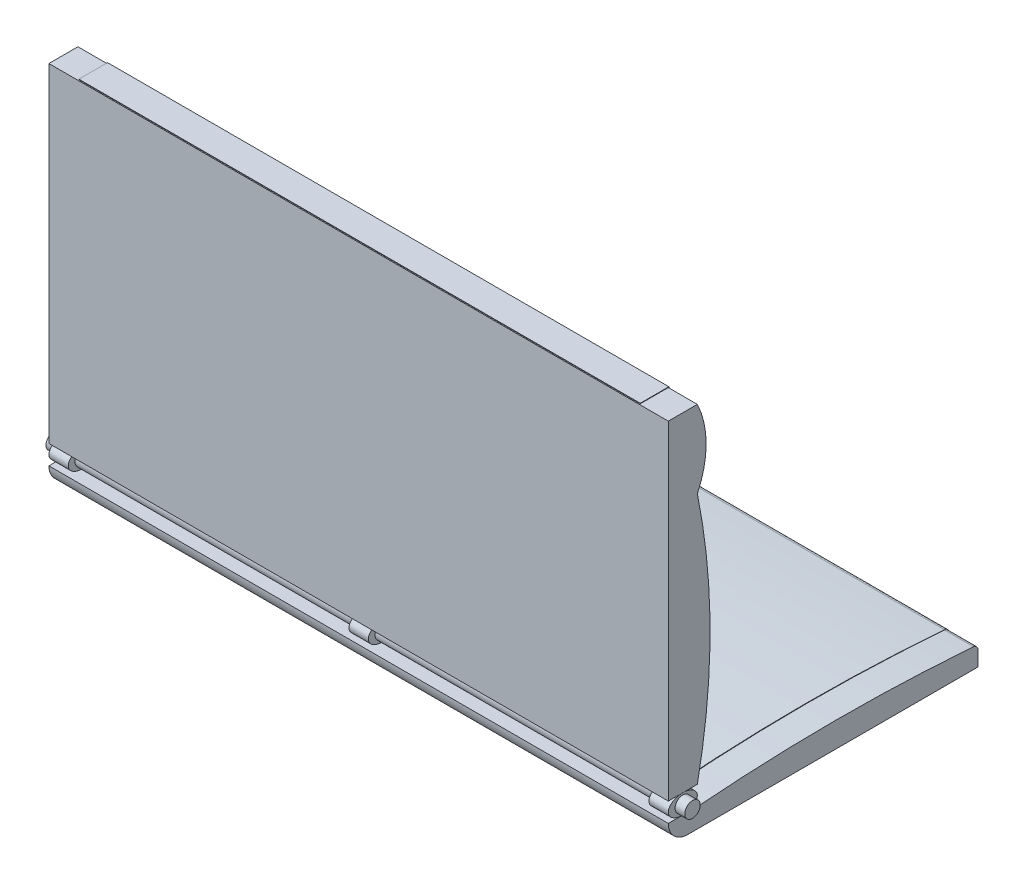
SolidWorks part; units mm, degrees
ref_plane "Front Plane" through (0, 0, 0) normal (0, 0, 1) x (1, 0, 0)
ref_plane "Top Plane" through (0, 0, 0) normal (0, 1, 0) x (1, 0, 0)
ref_plane "Right Plane" through (0, 0, 0) normal (1, 0, 0) x (0, 0, -1)
sketch "Sketch2" plane through (0, 0, 0) normal (0, 1, 0) x (1, 0, 0)
  line L1 (-406.4, -203.2) -> (406.4, -203.2)
  line L2 (-406.4, -203.2) -> (-406.4, 203.2)
  line L3 (-406.4, 203.2) -> (406.4, 203.2)
  line L4 (406.4, -203.2) -> (406.4, 203.2)
  line L5 (-406.4, -203.2) -> (406.4, 203.2) construction
  line L6 (-406.4, 203.2) -> (406.4, -203.2) construction
  point P0 (0, 0)
extrude "Boss-Extrude1" add sketch "Sketch2" along normal blind 25.4
sketch "Sketch3" plane through (0, 25.4, 0) normal (0, 1, 0) x (1, 0, 0)
  line L0 (406.4, -203.2) -> (406.4, 203.2) construction
  line L1 (-406.4, -203.2) -> (406.4, -203.2)
  line L2 (-406.4, -203.2) -> (-406.4, -165.1)
  line L3 (-406.4, -165.1) -> (406.4, -165.1)
  line L4 (406.4, -203.2) -> (406.4, -165.1)
extrude "Boss-Extrude2" add sketch "Sketch3" along normal blind 431.8 from offset 25.4 separate body
sketch "Sketch4" plane through (406.4, 0, 0) normal (1, 0, 0) x (0, 0, -1)
  line L0 (-203.2, 50.8) -> (-203.2, 25.4) construction
  line L1 (-203.2, 25.4) -> (-165.1, 50.8) construction
  line L2 (-165.1, 50.8) -> (-165.1, 25.4) construction
  line L3 (-203.2, 25.4) -> (203.2, 25.4) construction
  line L4 (-165.1, 25.4) -> (-203.2, 50.8) construction
  line L5 (-203.2, 50.8) -> (-165.1, 50.8) construction
  ellipse E0 centre (-184.15, 38.1) end of major axis (-203.2, 38.1) minor radius 12.7
extrude "Boss-Extrude3" add sketch "Sketch4" against normal blind 25.4 separate body
sketch "Sketch6" plane through (-406.4, 0, 0) normal (-1, 0, 0) x (0, 0, 1)
  line L0 (203.2, 50.8) -> (203.2, 25.4) construction
  line L1 (203.2, 25.4) -> (165.1, 50.8) construction
  line L2 (165.1, 50.8) -> (165.1, 25.4) construction
  line L3 (-203.2, 25.4) -> (203.2, 25.4) construction
  line L4 (165.1, 25.4) -> (203.2, 50.8) construction
  line L5 (165.1, 50.8) -> (203.2, 50.8) construction
  ellipse E0 centre (184.15, 38.1) end of major axis (203.2, 38.1) minor radius 12.7
extrude "Boss-Extrude4" add sketch "Sketch6" against normal blind 25.4 separate body
sketch "Sketch7" plane through (406.4, 0, 0) normal (1, 0, 0) x (0, 0, -1)
  line L0 (-203.2, 50.8) -> (-203.2, 25.4) construction
  line L1 (-203.2, 25.4) -> (-165.1, 50.8) construction
  line L2 (-165.1, 50.8) -> (-165.1, 25.4) construction
  line L3 (-203.2, 25.4) -> (203.2, 25.4) construction
  line L4 (-165.1, 25.4) -> (-203.2, 50.8) construction
  line L5 (-203.2, 50.8) -> (-165.1, 50.8) construction
  ellipse E0 centre (-184.15, 38.1) end of major axis (-203.2, 38.1) minor radius 12.7
extrude "Boss-Extrude5" add sketch "Sketch7" along normal blind 25.4 from offset 419.1 separate body offset against normal yes
sketch "Sketch8" plane through (406.4, 0, 0) normal (1, 0, 0) x (0, 0, -1)
  circle A0 centre (-184.15, 38.1) radius 10.16
extrude "Boss-Extrude6" add sketch "Sketch8" against normal blind 838.2 from offset 12.7
sketch "Sketch9" plane through (-406.4, 0, 0) normal (-1, 0, 0) x (0, 0, 1)
  line L0 (203.2, 25.4) -> (165.1, 50.8) construction
  line L1 (165.1, 50.8) -> (165.1, 25.4) construction
  line L2 (-203.2, 25.4) -> (203.2, 25.4) construction
  line L3 (165.1, 25.4) -> (165.1, 0)
  line L4 (-203.2, 0) -> (203.2, 0) construction
  line L5 (165.1, 0) -> (-203.2, 0)
  line L6 (-203.2, 0) -> (-203.2, 25.4)
  arc A0 (-203.2, 25.4) -> (165.1, 25.4) centre (-19.05, -2245.366) cw
extrude "Boss-Extrude7" add sketch "Sketch9" against normal blind 812.8
sketch "Sketch10" plane through (-406.4, 0, 0) normal (-1, 0, 0) x (0, 0, 1)
  line L0 (165.1, 482.6) -> (165.1, 381) construction
  line L1 (165.1, 482.6) -> (165.1, 50.8) construction
  line L2 (165.1, 482.6) -> (203.2, 482.6)
  line L3 (203.2, 482.6) -> (203.2, 381)
  line L4 (203.2, 482.6) -> (203.2, 50.8) construction
  line L5 (203.2, 381) -> (165.1, 381)
  line L6 (165.1, 50.8) -> (203.2, 50.8)
  line L7 (203.2, 50.8) -> (203.2, 381)
  line L8 (203.2, 381) -> (165.1, 381)
  line L9 (165.1, 50.8) -> (203.2, 50.8)
  line L10 (203.2, 381) -> (165.1, 381)
  line L11 (203.2, 381) -> (203.2, 50.8)
  arc A0 (165.1, 482.6) -> (165.1, 381) centre (270.9064, 431.8) ccw
  arc A1 (165.1, 381) -> (165.1, 50.8) centre (972.649, 215.9) ccw
  line M2 (165.1, 50.8) -> (203.2, 50.8)
  line M3 (203.2, 50.8) -> (203.2, 482.6)
  line M4 (203.2, 482.6) -> (165.1, 482.6)
  line M5 (165.1, 482.6) -> (165.1, 50.8)
extrude "Boss-Extrude8" add sketch "Sketch10" against normal blind 812.8 contours L5 M3 M4 M5 | A1 M5 | L5 M3 M5 M2 | A0 L2 L3 L5 region at (-406.4, 431.8, 184.15) region at (-406.4, 215.9, 158.4125) region at (-406.4, 215.9, 184.15)
fillet "Fillet1" radius 25.4 1 edges at (0, 0, 203.2)
fillet "Fillet2" radius 6.35 1 edges at (0, 25.4, -203.2)
sketch "Sketch11" plane through (-406.4, 0, 0) normal (-1, 0, 0) x (0, 0, 1)
  line L0 (165.1, 482.6) -> (203.2, 482.6) construction
  line L1 (203.2, 482.6) -> (201.93, 482.6) construction
  line L2 (201.93, 482.6) -> (201.93, 483.235) construction
  line L3 (201.93, 482.6) -> (201.93, 483.235)
  line L4 (201.93, 483.235) -> (164.338, 483.235)
  line L5 (164.338, 50.1749) -> (184.15, 50.8)
  line L6 (165.1, 50.8) -> (203.2, 50.8) construction
  line L7 (201.93, 482.6) -> (201.93, 50.8)
  line L8 (201.93, 50.8) -> (184.15, 50.8)
  arc A0 (164.338, 483.235) -> (164.338, 380.5081) centre (270.4903, 431.8715) ccw
  arc A1 (164.338, 380.5081) -> (164.338, 50.1749) centre (911.4385, 215.3415) ccw
extrude "Boss-Extrude10" add sketch "Sketch11" against normal blind 736.6 from offset 38.1 separate body offset against normal yes
sketch "Sketch12" plane through (-406.4, 0, 0) normal (-1, 0, 0) x (0, 0, 1)
  line L0 (-203.2, 0.4199) -> (-203.4723, 0.4199)
  line L1 (-203.2, 19.5365) -> (-203.2, 0) construction
  line L2 (-203.4723, 0.4199) -> (-203.4723, 19.5157)
  line L3 (164.9545, 26.1401) -> (184.15, 25.4)
  line L4 (165.1, 25.4) -> (203.2, 25.4) construction
  line L5 (184.15, 25.4) -> (202.8265, 25.4)
  line L6 (-203.2, 0.4199) -> (177.698, 0.4199)
  arc A0 (-203.4723, 19.5157) -> (-197.3334, 26.1401) centre (-197.0907, 19.7584) cw
  arc A1 (-197.3334, 26.1401) -> (164.9545, 26.1401) centre (-16.1894, -2187.1393) cw
  arc A2 (177.698, 0.4199) -> (202.8265, 25.4) centre (176.9654, 26.2858) ccw
extrude "Boss-Extrude12" add sketch "Sketch12" against normal blind 736.6 from offset 38.1 separate body offset against normal yes
sketch "Sketch13" plane through (0, 0, 0) normal (0, -1, 0) x (1, 0, 0)
  line L0 (0, 0) -> (3.988, 0)
  line L1 (3.988, 0) -> (0, 5.288)
  line L2 (0, 5.288) -> (0, 0)
extrude "Boss-Extrude13" add sketch "Sketch13" along normal blind 6.35 contours L2 L0 L1
